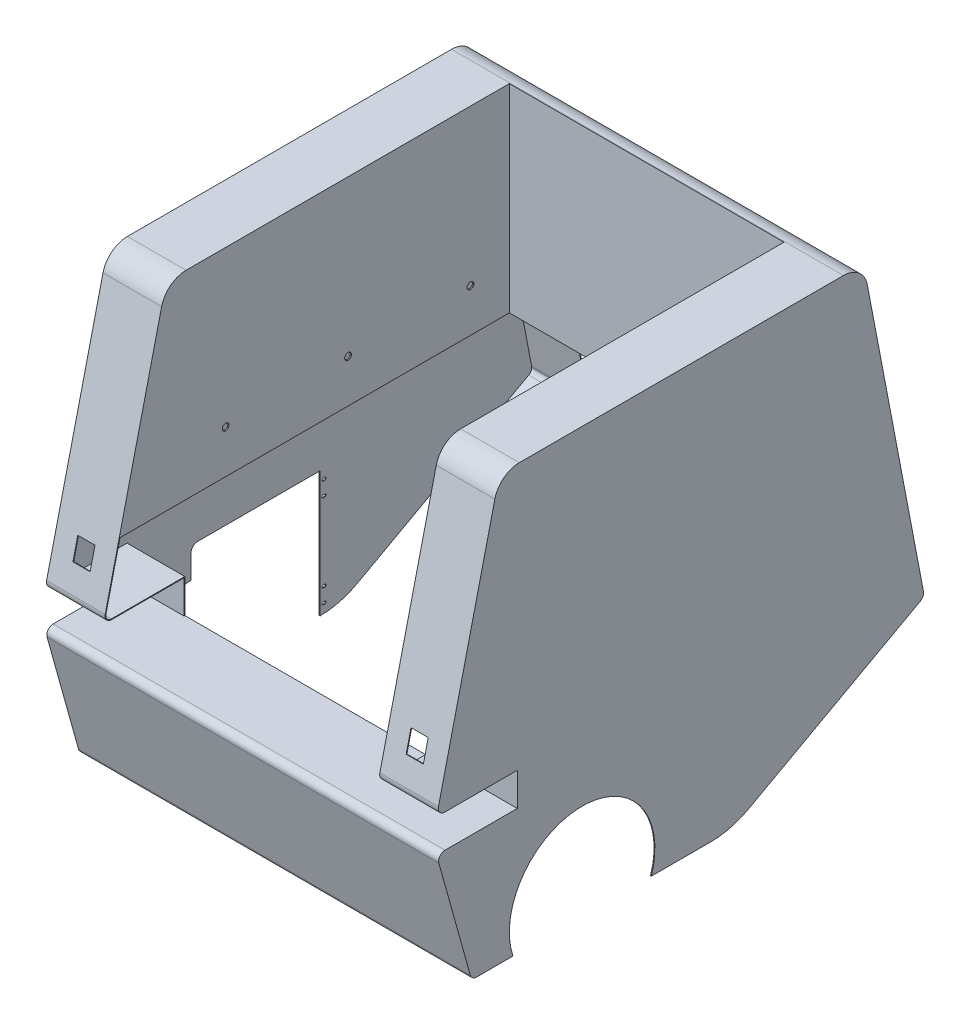
SolidWorks part; units mm, degrees
material "6061 합금"
ref_plane "정면" through (0, 0, 0) normal (0, 0, 1) x (1, 0, 0)
ref_plane "윗면" through (0, 0, 0) normal (0, 1, 0) x (1, 0, 0)
ref_plane "우측면" through (0, 0, 0) normal (1, 0, 0) x (0, 0, -1)
sketch "스케치1" plane through (0, 0, 0) normal (0, 1, 0) x (1, 0, 0)
  line L2 (-295, 336) -> (-295, -336)
  line L3 (-295, -336) -> (295, -336)
  line L4 (295, 336) -> (295, -336)
  line L5 (-295, 336) -> (295, -336) construction
  line L6 (-295, -336) -> (295, 336) construction
  line L8 (-295, 336) -> (-295, 399)
  line L9 (-295, 399) -> (295, 399)
  line L10 (295, 336) -> (295, 399)
  point P0 (0, 0)
  dimension "D1" = 590
  dimension "D2" = 672
  dimension "D3" = 63
extrude "보스-돌출1" add sketch "스케치1" along normal blind 640
shell "쉘1" thickness 1.2 removed face at (0, 0, -31.5) outward yes
sketch "스케치2" plane through (296.2, 0, 0) normal (1, 0, 0) x (0, 0, -1)
  line L0 (-212.2, 641.2) -> (-212.2, 0) construction
  line L1 (-337.2, 641.2) -> (400.2, 641.2) construction
  line L2 (-337.2, 0) -> (400.2, 0) construction
  line L3 (-337.2, 641.2) -> (-337.2, 0) construction
  line L4 (-182.2, 641.2) -> (-182.2, 0) construction
  line L5 (277.8, 641.2) -> (277.8, 160) construction
  line L6 (247.8, 641.2) -> (247.8, 160) construction
  line L8 (-212.2, 190) -> (277.8, 190) construction
  line L9 (-212.2, 160) -> (277.8, 160) construction
  line L10 (-212.2, 340) -> (277.8, 340) construction
  line L11 (-212.2, 310) -> (277.8, 310) construction
  line L12 (-212.2, 421) -> (277.8, 421) construction
  line L13 (-212.2, 391) -> (277.8, 391) construction
  line L14 (77.8, 0) -> (77.8, 190) construction
  line L15 (47.8, 190) -> (47.8, 0) construction
  line L16 (187.8, 190) -> (187.8, 160) construction
  line L17 (157.8, 190) -> (157.8, 160) construction
  line L18 (-147.2, 34) -> (-147.2, 0)
  line L19 (-147.2, 0) -> (-87.2, 0)
  line L20 (-87.2, 0) -> (-87.2, 34)
  line L21 (-215.2, 190) -> (-284.2, 190) construction
  line L22 (-284.2, 190) -> (-284.2, 195) construction
  line L23 (-284.2, 195) -> (-212.2, 195) construction
  line L24 (-215.2, 240) -> (-215.2, 190)
  line L25 (-284.2, 195) -> (-284.2, 240) construction
  line L26 (-284.2, 240) -> (-215.2, 240) construction
  line L29 (-333.7807, 177.7423) -> (-286.171, 7.0657)
  line L30 (-276.8646, 0) -> (77.8, 0)
  line L31 (-212.2, 641.2) -> (277.8, 641.2)
  line L32 (-324.4743, 190) -> (-215.2, 190)
  line L34 (-215.2, 240) -> (-324.9833, 240)
  line L35 (-248.2, 195) -> (-248.2, 240) construction
  line L36 (-334.3851, 251.8879) -> (-249.1125, 612.0072)
  line L40 (-212.2, 340) -> (-313.521, 340) construction
  line L42 (-337.2, 641.2) -> (400.2, 641.2) construction
  line L43 (313.8942, 611.3536) -> (398.832, 167.1542)
  line L44 (400.2, 641.2) -> (400.2, 0) construction
  line L45 (393.8102, 156.5036) -> (134.1176, 14.4009)
  line L46 (-337.2, 0) -> (400.2, 0) construction
  line L48 (-314.9744, 329.5224) -> (-326.4708, 280.9713) construction
  arc A0 (-87.2, 34) -> (-147.2, 34) centre (-117.2, 34) ccw
  arc A3 (-276.8646, 0) -> (-286.171, 7.0657) centre (-276.8646, 9.6617) cw
  arc A4 (-333.7807, 177.7423) -> (-324.4743, 190) centre (-324.4743, 180.3383) cw
  arc A5 (-324.9833, 240) -> (-334.3851, 251.8879) centre (-324.9833, 249.6617) cw
  arc A9 (398.832, 167.1542) -> (393.8102, 156.5036) centre (389.01, 165.2761) cw
  arc A11 (313.8942, 611.3536) -> (277.8, 641.2) centre (277.8, 604.4519) ccw
  arc A12 (77.8, 0) -> (134.1176, 14.4009) centre (77.8, 117.3212) ccw
  arc A13 (-212.2, 641.2) -> (-249.1125, 612.0072) centre (-212.2, 603.2667) ccw
  point P34 (187.8, 175)
  point P55 (-242.2, 641.2)
  point P63 (-284.2, 0)
  point P66 (-337.2, 190)
  point P69 (-337.2, 240)
  point P74 (307.8, 641.2)
  point P77 (107.8, 0)
  point P80 (400.2, 160)
  line M12 (-337.2, 0) -> (400.2, 0)
  line M14 (400.2, 641.2) -> (-337.2, 641.2)
  line M15 (-337.2, 641.2) -> (-337.2, 0)
  line M74 (400.2, 0) -> (400.2, 641.2)
  dimension "D17" = 60
  dimension "D23" = 30
  dimension "D24" = 30
  dimension "D27" = 10
  dimension "D30" = 1
  dimension "D1" = 125
  dimension "D2" = 30
  dimension "D3" = 490
  dimension "D4" = 30
  dimension "D5" = 190
  dimension "D6" = 30
  dimension "D7" = 150
  dimension "D8" = 30
  dimension "D9" = 81
  dimension "D10" = 30
  dimension "D11" = 290
  dimension "D12" = 30
  dimension "D13" = 110
  dimension "D14" = 30
  dimension "D15" = 95
  dimension "D16" = 34
  dimension "D18" = 72
  dimension "D19" = 5
  dimension "D20" = 45
  dimension "D22" = 30
  dimension "D28" = 3
  dimension "D29" = 72
extrude "컷-돌출1" cut sketch "스케치2" against normal up to next contours L34 A5 L36 A3 L29 A4 L32 M14 M15 M12 | L43 A9 L45 M12 M74 M14 region at (296.2, 6.5327, 307.0323) region at (296.2, 2.9619, -107.0426)
sketch "스케치3" plane through (-295, 0, 0) normal (1, 0, 0) x (0, 0, -1)
  line L10 (-247.9448, 611.7307) -> (-333.2174, 251.6114)
  line L11 (-324.9833, 241.2) -> (-214, 241.2)
  line L15 (-214, 241.2) -> (-214, 188.8)
  line L17 (-214, 188.8) -> (-324.4743, 188.8)
  line L18 (-332.6249, 178.0647) -> (-285.0151, 7.3881)
  line L20 (291.7052, 102) -> (393.2342, 157.5563)
  line L21 (397.8, 164.8576) -> (397.8, 165.6946)
  line L33 (397.6534, 166.9288) -> (312.7156, 611.1283)
  line L55 (287.1143, 640) -> (-221.6657, 640)
  line L56 (-249.1125, 612.0072) -> (-334.3851, 251.8879)
  line L58 (-324.9833, 240) -> (-215.2, 240)
  line L60 (-215.2, 240) -> (-215.2, 190)
  line L61 (-215.2, 190) -> (-324.4743, 190)
  line L62 (-333.7807, 177.7423) -> (-286.171, 7.0657)
  line L63 (-276.8646, 0) -> (77.8, 0)
  line L64 (134.1176, 14.4009) -> (393.8102, 156.5036)
  line L65 (399, 164.83) -> (399, 165.7222)
  line L66 (398.832, 167.1542) -> (313.8942, 611.3536)
  line L67 (287.1143, 640) -> (277.8, 640)
  line L68 (-249.1125, 612.0072) -> (-334.3851, 251.8879)
  line L69 (-324.9833, 240) -> (-215.2, 240)
  line L70 (-215.2, 240) -> (-215.2, 190)
  line L71 (-215.2, 190) -> (-324.4743, 190)
  line L72 (-333.7807, 177.7423) -> (-286.171, 7.0657)
  line L74 (292.2812, 100.9473) -> (393.8102, 156.5036)
  line L75 (399, 164.83) -> (399, 165.7222)
  line L76 (398.832, 167.1542) -> (313.8942, 611.3536)
  line L77 (277.8, 160) -> (277.8, 102) construction
  line L78 (277.8, 102) -> (298.7222, 102) construction
  line L79 (291.7052, 102) -> (292.2812, 100.9473)
  line L80 (134.1176, 14.4009) -> (393.8102, 156.5036) construction
  line L81 (133.5415, 15.4536) -> (393.2342, 157.5563) construction
  line L82 (-212.2, 640) -> (-221.6657, 640)
  line L83 (287.1143, 640) -> (-221.6657, 640) construction
  line L84 (-276.8646, 1.2) -> (-276.8646, 0)
  line L112 (286.9584, 638.8) -> (-221.5123, 638.8) construction
  line L113 (-276.8646, 1.2) -> (77.8, 1.2) construction
  line L114 (-276.8646, 0) -> (77.8, 0) construction
  arc A37 (-221.5123, 638.8) -> (-247.9448, 611.7307) centre (-212.2, 603.2667) ccw
  arc A38 (-333.2174, 251.6114) -> (-324.9833, 241.2) centre (-324.9833, 249.6617) ccw
  arc A39 (-324.4743, 188.8) -> (-332.6249, 178.0647) centre (-324.4743, 180.3383) ccw
  arc A40 (-285.0151, 7.3881) -> (-276.8646, 1.2) centre (-276.8646, 9.6617) ccw
  arc A42 (393.2342, 157.5563) -> (397.8, 164.8576) centre (389.01, 165.2761) ccw
  arc A43 (397.8, 165.6946) -> (397.6534, 166.9288) centre (389.01, 165.2761) ccw
  arc A45 (312.7156, 611.1283) -> (286.9584, 638.8) centre (277.8, 604.4519) ccw
  arc A55 (-221.6657, 640) -> (-249.1125, 612.0072) centre (-212.2, 603.2667) ccw
  arc A56 (-334.3851, 251.8879) -> (-324.9833, 240) centre (-324.9833, 249.6617) ccw
  arc A57 (-324.4743, 190) -> (-333.7807, 177.7423) centre (-324.4743, 180.3383) ccw
  arc A58 (-286.171, 7.0657) -> (-276.8646, 0) centre (-276.8646, 9.6617) ccw
  arc A59 (77.8, 0) -> (134.1176, 14.4009) centre (77.8, 117.3212) ccw
  arc A60 (393.8102, 156.5036) -> (399, 164.83) centre (389.01, 165.2761) ccw
  arc A61 (399, 165.7222) -> (398.832, 167.1542) centre (389.01, 165.2761) ccw
  arc A62 (313.8942, 611.3536) -> (287.1143, 640) centre (277.8, 604.4519) ccw
  arc A63 (-221.6657, 640) -> (-249.1125, 612.0072) centre (-212.2, 603.2667) ccw
  arc A64 (-334.3851, 251.8879) -> (-324.9833, 240) centre (-324.9833, 249.6617) ccw
  arc A65 (-324.4743, 190) -> (-333.7807, 177.7423) centre (-324.4743, 180.3383) ccw
  arc A66 (-286.171, 7.0657) -> (-276.8646, 0) centre (-276.8646, 9.6617) ccw
  arc A68 (393.8102, 156.5036) -> (399, 164.83) centre (389.01, 165.2761) ccw
  arc A72 (399, 165.7222) -> (398.832, 167.1542) centre (389.01, 165.2761) ccw
  arc A74 (313.8942, 611.3536) -> (287.1143, 640) centre (277.8, 604.4519) ccw
  arc A76 (286.9584, 638.8) -> (277.8, 640) centre (277.8, 604.4519) ccw
  arc A79 (-221.5123, 638.8) -> (-212.2, 640) centre (-212.2, 603.2667) cw
  arc A97 (77.8, 0) -> (134.1176, 14.4009) centre (77.8, 117.3212) ccw construction
  arc A98 (77.8, 1.2) -> (133.5415, 15.4536) centre (77.8, 117.3212) ccw construction
  line M28 (-249.1125, 612.0072) -> (-334.3851, 251.8879)
  arc M30 (-334.3851, 251.8879) -> (-324.9833, 240) centre (-324.9833, 249.6617) ccw
  line M31 (-324.9833, 240) -> (-215.2, 240)
  line M33 (-215.2, 190) -> (-324.4743, 190)
  arc M34 (-324.4743, 190) -> (-333.7807, 177.7423) centre (-324.4743, 180.3383) ccw
  line M35 (-333.7807, 177.7423) -> (-286.171, 7.0657)
  arc M36 (-286.171, 7.0657) -> (-276.8646, 0) centre (-276.8646, 9.6617) ccw
  line M43 (287.1143, 640) -> (-221.6657, 640)
  line M77 (134.1176, 14.4009) -> (393.8102, 156.5036)
  arc M78 (393.8102, 156.5036) -> (399, 164.83) centre (389.01, 165.2761) ccw
  line M79 (399, 164.83) -> (399, 165.7222)
  line M80 (398.832, 167.1542) -> (313.8942, 611.3536)
  line M121 (-215.2, 240) -> (-215.2, 190)
  arc M131 (399, 165.7222) -> (398.832, 167.1542) centre (389.01, 165.2761) ccw
  arc M132 (313.8942, 611.3536) -> (287.1143, 640) centre (277.8, 604.4519) ccw
  dimension "D2" = 1.2
  dimension "D3" = 58
  dimension "D1" = 0
extrude "보스-돌출2" add sketch "스케치3" along normal blind 590 contours A45 L33 M43 M28 M30 M31 M121 M33 M34 M35 M36 | M77 M78 M79 M131 M80 M132 M43 region at (-295, 431.8212, 291.2152) region at (-295, 629.1702, -304.241)
sketch "스케치4" plane through (-296.2, 0, 0) normal (-1, 0, 0) x (0, 0, 1)
  line L0 (-77.8, 190) -> (-77.8, 0)
  line L2 (-77.8, 0) -> (12.5864, 0)
  line L3 (147.2, 0) -> (147.2, 34)
  line L4 (87.2, 0) -> (147.2, 0)
  line L5 (87.2, 34) -> (87.2, 0)
  line L6 (147.2, 0) -> (147.2, 34)
  line L7 (87.2, 0) -> (147.2, 0)
  line L8 (87.2, 34) -> (87.2, 0)
  line L17 (286.171, 7.0657) -> (333.7807, 177.7423)
  line L18 (-77.8, 0) -> (276.8646, 0)
  line L21 (-393.8102, 156.5036) -> (-134.1176, 14.4009)
  line L22 (212.2, 641.2) -> (-277.8, 641.2)
  line L24 (334.3851, 251.8879) -> (249.1125, 612.0072)
  line L25 (215.2, 240) -> (324.9833, 240)
  line L26 (215.2, 190) -> (215.2, 240)
  line L27 (324.4743, 190) -> (215.2, 190)
  line L28 (286.171, 7.0657) -> (333.7807, 177.7423)
  line L29 (-77.8, 0) -> (276.8646, 0)
  line L33 (212.2, 641.2) -> (-277.8, 641.2)
  line L35 (334.3851, 251.8879) -> (249.1125, 612.0072)
  line L36 (215.2, 240) -> (324.9833, 240)
  line L38 (324.4743, 190) -> (215.2, 190)
  line L46 (215.2, 190) -> (215.2, 240)
  line L47 (215.2, 190) -> (215.2, 240)
  line L48 (215.2, 190) -> (215.2, 240)
  line L79 (117.2, 144) -> (117.2, 180)
  line L80 (212.2, 190) -> (-277.8, 190) construction
  line L81 (107.2, 190) -> (-77.8, 190)
  line L91 (-393.8102, 156.5036) -> (-134.1176, 14.4009)
  line L92 (-313.8942, 611.3536) -> (-398.832, 167.1542)
  line L93 (-313.8942, 611.3536) -> (-398.832, 167.1542)
  line L102 (286.171, 7.0657) -> (333.7807, 177.7423)
  line L103 (-77.8, 0) -> (276.8646, 0)
  line L105 (-393.8102, 156.5036) -> (-134.1176, 14.4009)
  line L106 (-313.8942, 611.3536) -> (-398.832, 167.1542)
  line L108 (212.2, 641.2) -> (-277.8, 641.2)
  line L110 (334.3851, 251.8879) -> (249.1125, 612.0072)
  line L111 (215.2, 240) -> (324.9833, 240)
  line L113 (324.4743, 190) -> (215.2, 190)
  line L114 (286.171, 7.0657) -> (333.7807, 177.7423)
  line L115 (-77.8, 0) -> (276.8646, 0)
  line L117 (-393.8102, 156.5036) -> (-134.1176, 14.4009)
  line L118 (-313.8942, 611.3536) -> (-398.832, 167.1542)
  line L120 (212.2, 641.2) -> (-277.8, 641.2)
  line L122 (334.3851, 251.8879) -> (249.1125, 612.0072)
  line L123 (215.2, 240) -> (324.9833, 240)
  line L125 (324.4743, 190) -> (215.2, 190)
  arc A0 (117.2, 180) -> (107.2, 190) centre (107.2, 180) ccw
  arc A1 (147.2, 34) -> (87.2, 34) centre (117.2, 34) ccw
  arc A2 (147.2, 34) -> (87.2, 34) centre (117.2, 34) ccw
  circle A3 centre (117.2, 34) radius 105 construction
  arc A8 (276.8646, 0) -> (286.171, 7.0657) centre (276.8646, 9.6617) ccw
  arc A9 (-134.1176, 14.4009) -> (-77.8, 0) centre (-77.8, 117.3212) ccw
  arc A11 (249.1125, 612.0072) -> (212.2, 641.2) centre (212.2, 603.2667) ccw
  arc A12 (324.9833, 240) -> (334.3851, 251.8879) centre (324.9833, 249.6617) ccw
  arc A13 (333.7807, 177.7423) -> (324.4743, 190) centre (324.4743, 180.3383) ccw
  arc A14 (276.8646, 0) -> (286.171, 7.0657) centre (276.8646, 9.6617) ccw
  arc A18 (324.9833, 240) -> (334.3851, 251.8879) centre (324.9833, 249.6617) ccw
  arc A19 (333.7807, 177.7423) -> (324.4743, 190) centre (324.4743, 180.3383) ccw
  arc A22 (-134.1176, 14.4009) -> (-77.8, 0) centre (-77.8, 117.3212) ccw
  arc A23 (-277.8, 641.2) -> (-313.8942, 611.3536) centre (-277.8, 604.4519) ccw
  arc A24 (-277.8, 641.2) -> (-313.8942, 611.3536) centre (-277.8, 604.4519) ccw
  arc A25 (-134.1176, 14.4009) -> (-77.8, 0) centre (-77.8, 117.3212) ccw
  arc A26 (-134.1176, 14.4009) -> (-77.8, 0) centre (-77.8, 117.3212) ccw
  arc A27 (-277.8, 641.2) -> (-313.8942, 611.3536) centre (-277.8, 604.4519) ccw
  arc A28 (-277.8, 641.2) -> (-313.8942, 611.3536) centre (-277.8, 604.4519) ccw
  arc A30 (249.1125, 612.0072) -> (212.2, 641.2) centre (212.2, 603.2667) ccw
  arc A31 (249.1125, 612.0072) -> (212.2, 641.2) centre (212.2, 603.2667) ccw
  arc A32 (249.1125, 612.0072) -> (212.2, 641.2) centre (212.2, 603.2667) ccw
  circle A38 centre (117.2, 34) radius 110
  arc A45 (-398.832, 167.1542) -> (-393.8102, 156.5036) centre (-389.01, 165.2761) ccw
  arc A46 (-398.832, 167.1542) -> (-393.8102, 156.5036) centre (-389.01, 165.2761) ccw
  arc A52 (276.8646, 0) -> (286.171, 7.0657) centre (276.8646, 9.6617) ccw
  arc A54 (-398.832, 167.1542) -> (-393.8102, 156.5036) centre (-389.01, 165.2761) ccw
  arc A57 (324.9833, 240) -> (334.3851, 251.8879) centre (324.9833, 249.6617) ccw
  arc A58 (333.7807, 177.7423) -> (324.4743, 190) centre (324.4743, 180.3383) ccw
  arc A59 (276.8646, 0) -> (286.171, 7.0657) centre (276.8646, 9.6617) ccw
  arc A61 (-398.832, 167.1542) -> (-393.8102, 156.5036) centre (-389.01, 165.2761) ccw
  arc A64 (324.9833, 240) -> (334.3851, 251.8879) centre (324.9833, 249.6617) ccw
  arc A65 (333.7807, 177.7423) -> (324.4743, 190) centre (324.4743, 180.3383) ccw
  point P42 (117.2, 190)
  line M24 (-77.8, 0) -> (276.8646, 0)
  dimension "D3" = 220
  dimension "D4" = 10
  dimension "D1" = 0
  dimension "D2" = 0
  dimension "D5" = 0
extrude "컷-돌출2" cut sketch "스케치4" against normal up to next contours A38 M24 | A38 L8 A2 L6 M24 | L6 A2 L8 M24 | A38 L79 A0 L81 L0 M24 region at (-296.2, 112.6357, -7.3305) region at (-296.2, 68.0406, 117.2) region at (-296.2, -31.53, 117.2) region at (-296.2, 29.1704, 117.2)
sketch "스케치5" plane through (296.2, 0, 0) normal (1, 0, 0) x (0, 0, -1)
  line L3 (-147.2, 34) -> (-147.2, 0)
  line L4 (-147.2, 0) -> (-87.2, 0)
  line L5 (-87.2, 0) -> (-87.2, 34)
  line L6 (-147.2, 34) -> (-147.2, 0)
  line L7 (-147.2, 0) -> (-87.2, 0)
  line L8 (-87.2, 0) -> (-87.2, 34)
  line L18 (-333.7807, 177.7423) -> (-286.171, 7.0657)
  line L19 (-276.8646, 0) -> (77.8, 0)
  line L21 (134.1176, 14.4009) -> (393.8102, 156.5036)
  line L22 (398.832, 167.1542) -> (313.8942, 611.3536)
  line L24 (277.8, 641.2) -> (-212.2, 641.2)
  line L26 (-249.1125, 612.0072) -> (-334.3851, 251.8879)
  line L27 (-324.9833, 240) -> (-215.2, 240)
  line L28 (-215.2, 240) -> (-215.2, 190)
  line L29 (-215.2, 190) -> (-324.4743, 190)
  line L30 (-333.7807, 177.7423) -> (-286.171, 7.0657)
  line L31 (-276.8646, 0) -> (77.8, 0)
  line L33 (134.1176, 14.4009) -> (393.8102, 156.5036)
  line L34 (398.832, 167.1542) -> (313.8942, 611.3536)
  line L36 (277.8, 641.2) -> (-212.2, 641.2)
  line L38 (-249.1125, 612.0072) -> (-334.3851, 251.8879)
  line L39 (-324.9833, 240) -> (-215.2, 240)
  line L41 (-215.2, 190) -> (-324.4743, 190)
  line L42 (-215.2, 240) -> (-215.2, 190)
  circle A0 centre (-117.2, 34) radius 110
  arc A1 (-87.2, 34) -> (-147.2, 34) centre (-117.2, 34) ccw
  arc A2 (-87.2, 34) -> (-147.2, 34) centre (-117.2, 34) ccw
  circle A3 centre (-117.2, 34) radius 105 construction
  arc A9 (-286.171, 7.0657) -> (-276.8646, 0) centre (-276.8646, 9.6617) ccw
  arc A10 (77.8, 0) -> (134.1176, 14.4009) centre (77.8, 117.3212) ccw
  arc A11 (393.8102, 156.5036) -> (398.832, 167.1542) centre (389.01, 165.2761) ccw
  arc A12 (77.8, 0) -> (134.1176, 14.4009) centre (77.8, 117.3212) ccw
  arc A13 (-212.2, 641.2) -> (-249.1125, 612.0072) centre (-212.2, 603.2667) ccw
  arc A14 (-334.3851, 251.8879) -> (-324.9833, 240) centre (-324.9833, 249.6617) ccw
  arc A15 (-324.4743, 190) -> (-333.7807, 177.7423) centre (-324.4743, 180.3383) ccw
  arc A16 (-286.171, 7.0657) -> (-276.8646, 0) centre (-276.8646, 9.6617) ccw
  arc A18 (393.8102, 156.5036) -> (398.832, 167.1542) centre (389.01, 165.2761) ccw
  arc A21 (-334.3851, 251.8879) -> (-324.9833, 240) centre (-324.9833, 249.6617) ccw
  arc A22 (-324.4743, 190) -> (-333.7807, 177.7423) centre (-324.4743, 180.3383) ccw
  arc A24 (313.8942, 611.3536) -> (277.8, 641.2) centre (277.8, 604.4519) ccw
  arc A25 (313.8942, 611.3536) -> (277.8, 641.2) centre (277.8, 604.4519) ccw
  arc A27 (-212.2, 641.2) -> (-249.1125, 612.0072) centre (-212.2, 603.2667) ccw
  line M26 (-276.8646, 0) -> (77.8, 0)
  dimension "D3" = 220
  dimension "D1" = 0
  dimension "D2" = 0
extrude "컷-돌출3" cut sketch "스케치5" against normal up to next contours A2 L8 A0 L31 L6 M26 | L8 A2 L6 M26 | L31 A0 M26 region at (296.2, 29.1704, 117.2) region at (296.2, 68.0406, 117.2) region at (296.2, -31.53, 117.2)
ref_plane "평면1" through (0, 0, 350) normal (0, 0, 1) x (1, 0, 0)
sketch "스케치6" plane through (0, 0, 350) normal (0, 0, 1) x (1, 0, 0)
  line L0 (0, 0) -> (0, 641.2) construction
  line L2 (-240, 421) -> (-240, 0) construction
  line L3 (-207.6, 641.2) -> (207.6, 641.2)
  line L4 (240, 421) -> (240, 0) construction
  line L5 (-210, 421) -> (-210, 0) construction
  line L6 (210, 0) -> (210, 421) construction
  line L7 (-240, 30) -> (240, 30) construction
  line L8 (-240, 0) -> (240, 0) construction
  line L9 (-240, 160) -> (240, 160) construction
  line L10 (-240, 190) -> (240, 190) construction
  line L11 (-240, 310) -> (240, 310) construction
  line L12 (-240, 340) -> (240, 340) construction
  line L13 (210, 421) -> (240, 421) construction
  line L14 (210, 391) -> (240, 391) construction
  line L15 (-240, 421) -> (-210, 421) construction
  line L16 (-240, 391) -> (-210, 391) construction
  line L17 (-207.6, 339) -> (207.6, 339)
  line L22 (-207.6, 339) -> (-207.6, 641.2)
  line L24 (207.6, 339) -> (207.6, 641.2)
  line L27 (-296.2, 641.2) -> (296.2, 641.2) construction
  point P29 (225, 421)
  dimension "D1" = 240
  dimension "D2" = 240
  dimension "D3" = 30
  dimension "D4" = 30
  dimension "D5" = 30
  dimension "D6" = 160
  dimension "D7" = 30
  dimension "D8" = 150
  dimension "D9" = 30
  dimension "D10" = 81
  dimension "D11" = 30
  dimension "D12" = 1
  dimension "D13" = 2.4
  dimension "D14" = 2.4
extrude "컷-돌출4" cut sketch "스케치6" against normal up to vertex contours L17 L24 L3 L22 region at (0, 490.1, 350) up to point (296.2, 641.2, -277.8)
ref_plane "평면2" through (0, 0, 313.7578) normal (0, 0, -1) x (-1, 0, 0)
sketch "스케치7" plane through (0, 0, 313.7578) normal (0, 0, -1) x (-1, 0, 0)
  line L17 (207.6, 339) -> (-207.6, 339) construction
  line L18 (207.6, 339) -> (-207.6, 339)
  line L19 (207.6, 339) -> (207.6, 341.4)
  line L20 (207.6, 339) -> (207.6, 641.2) construction
  line L21 (207.6, 341.4) -> (-207.6, 341.4)
  line L22 (-207.6, 339) -> (-207.6, 641.2) construction
  line L23 (-207.6, 341.4) -> (-207.6, 339)
  dimension "D1" = 2.4
extrude "보스-돌출3" add sketch "스케치7" along normal up to vertex contours L21 region at (0, 340.2, 313.7578) up to point (296.2, 421, -277.8)
sketch "스케치8" plane through (0, 0, 0) normal (1, 0, 0) x (0, 0, -1)
  line L8 (-313.7578, 341.4) -> (-313.7578, 339)
  line L9 (-313.7578, 339) -> (-313.1895, 341.4)
  line L10 (-313.1895, 341.4) -> (-313.7578, 341.4)
  line L11 (-313.7578, 341.4) -> (-313.7578, 339)
  line L12 (-313.7578, 339) -> (-313.1895, 341.4)
  line L13 (-313.1895, 341.4) -> (-313.7578, 341.4)
  dimension "D1" = 0
extrude "컷-돌출5" cut sketch "스케치8" against normal through all both and the other way through all
sketch "스케치10" plane through (0, 341.4, 0) normal (0, 1, 0) x (1, 0, 0)
  line L14 (-207.6, 276.6) -> (207.6, 276.6)
  line L16 (-207.6, 277.8) -> (-208.8, 277.8)
  line L18 (-296.2, 277.8) -> (-207.6, 277.8) construction
  line L19 (-208.8, 277.8) -> (-208.8, -212.2)
  line L20 (-296.2, -212.2) -> (-207.6, -212.2) construction
  line L22 (-208.8, -212.2) -> (-207.6, -212.2)
  line L23 (-207.6, -311.9563) -> (-207.6, -313.1895)
  line L24 (-207.6, -313.1895) -> (207.6, -313.1895)
  line L26 (207.6, -313.1895) -> (207.6, -311.9563)
  line L27 (207.6, -311.9563) -> (207.6, 277.8)
  line L28 (207.6, 277.8) -> (-207.6, 277.8)
  line L29 (-207.6, 277.8) -> (-207.6, -311.9563)
  line L30 (-207.6, -311.9563) -> (-207.6, -313.1895)
  line L32 (207.6, -313.1895) -> (207.6, -311.9563)
  line L33 (207.6, -311.9563) -> (207.6, 277.8)
  line L34 (207.6, 277.8) -> (-207.6, 277.8)
  line L35 (-207.6, 277.8) -> (-207.6, -311.9563)
  line L36 (207.6, -212.2) -> (208.8, -212.2)
  line L37 (207.6, -212.2) -> (296.2, -212.2) construction
  line L38 (208.8, -212.2) -> (208.8, 277.8)
  line L39 (207.6, 277.8) -> (296.2, 277.8) construction
  line L40 (208.8, 277.8) -> (207.6, 277.8)
  line M13 (207.6, 277.8) -> (-207.6, 277.8)
  line M22 (207.6, -311.9563) -> (207.6, 277.8)
  line M23 (-207.6, 277.8) -> (-207.6, -311.9563)
  dimension "D1" = 0
  dimension "D2" = 1.2
  dimension "D3" = 1.2
  dimension "D4" = 1.2
extrude "보스-돌출4" add sketch "스케치10" along normal up to vertex contours M13 region at (0, 341.4, -277.2) up to point (296.2, 641.2, -277.8)
extrude "보스-돌출7" add sketch "스케치10<3>" along normal up to vertex and the other way up to vertex contours M23 | L38 L40 L33 L36 M22 region at (-208.2, 341.4, -32.8) region at (208.2, 341.4, -32.8) up to point (296.2, 641.2, -277.8) other way up to point (207.6, 339, -277.8)
sketch "스케치10<3>" plane through (0, 341.4, 0) normal (0, 1, 0) x (1, 0, 0) same geometry as "스케치10"
sketch "스케치30" plane through (-207.6, 0, 0) normal (1, 0, 0) x (0, 0, -1)
  line L0 (-247.9448, 611.7307) -> (-333.2174, 251.6114) construction
  line L1 (-247.9448, 611.7307) -> (-312.5246, 339)
  line L2 (-212.2, 339) -> (-312.5246, 339)
  line L3 (-212.2, 641.2) -> (-212.2, 0) construction
  line L4 (277.8, 339) -> (-212.2, 339) construction
  line L5 (-212.2, 339) -> (-212.2, 640)
  arc A0 (-212.2, 640) -> (-247.9448, 611.7307) centre (-212.2, 603.2667) ccw construction
  arc A1 (-212.2, 640) -> (-247.9448, 611.7307) centre (-212.2, 603.2667) ccw
extrude "보스-돌출8" add sketch "스케치30" against normal blind 1.2
mirror "대칭 복사2" about plane through (0, 0, 0) normal (1, 0, 0) of "보스-돌출8"
ref_plane "평면3" through (0, 0, -410) normal (0, 0, 1) x (1, 0, 0)
sketch "스케치15" plane through (0, 0, -410) normal (0, 0, 1) x (1, 0, 0)
  line L1 (-210, 340) -> (210, 340)
  line L2 (-210, 421) -> (-210, 0) construction
  line L3 (210, 340) -> (-210, 340)
  line L4 (210, 340) -> (210, 100.9473)
  line L5 (210, 100.9473) -> (-210, 100.9473)
  line L6 (-210, 340) -> (-210, 100.9473)
  line L8 (295, 100.9473) -> (-295, 100.9473) construction
  line L9 (-240, 340) -> (240, 340) construction
  line L10 (210, 0) -> (210, 421) construction
extrude "컷-돌출6" cut sketch "스케치15" along normal up to vertex contours L1 L6 L5 L4 region at (0, 220.4736, -410) up to point (296.2, 340, -277.8)
sketch "스케치17" plane through (0, 341.4, 0) normal (0, 1, 0) x (1, 0, 0)
  line L1 (209.8, -212.2) -> (-209.8, -212.2) construction
  line L3 (-209.8, 277.8) -> (209.8, 277.8) construction
  line L4 (-209.8, 247.8) -> (209.8, 247.8) construction
  line L7 (-209.8, -182.2) -> (209.8, -182.2) construction
  line L8 (-139.8, 247.8) -> (-139.8, -182.2) construction
  line L9 (-109.8, 247.8) -> (-109.8, -182.2) construction
  line L10 (139.8, 247.8) -> (139.8, -182.2) construction
  line L11 (109.8, 247.8) -> (109.8, -182.2) construction
  line L12 (-209.8, 187.8) -> (209.8, 187.8) construction
  line L13 (-209.8, 157.8) -> (209.8, 157.8) construction
  line L14 (-209.8, 77.8) -> (209.8, 77.8) construction
  line L15 (-209.8, 47.8) -> (209.8, 47.8) construction
  line L18 (-296.2, 277.8) -> (296.2, 277.8) construction
  line L19 (208.8, -312.5246) -> (208.8, 277.8) construction
  line L20 (-208.8, 277.8) -> (-208.8, -312.5246) construction
  point P24 (0, 157.8)
  dimension "D1" = 30
  dimension "D2" = 30
  dimension "D3" = 70
  dimension "D4" = 30
  dimension "D5" = 70
  dimension "D6" = 30
  dimension "D7" = 60
  dimension "D8" = 30
  dimension "D9" = 80
  dimension "D10" = 30
  dimension "D11" = 1
  dimension "D12" = 1
sketch "스케치18" plane through (0, 341.4, 0) normal (0, 1, 0) x (1, 0, 0)
  line L5 (-240, -350) -> (240, -350) construction
  line L6 (206.6, 275.6) -> (-206.6, 275.6)
  line L7 (-206.6, 275.6) -> (-206.6, -349)
  line L8 (-206.6, -349) -> (206.6, -349)
  line L9 (207.6, 276.6) -> (-207.6, 276.6)
  line L10 (-207.6, 276.6) -> (-207.6, -313.1895)
  line L11 (-207.6, -313.1895) -> (207.6, -313.1895)
  line L12 (207.6, -313.1895) -> (207.6, 276.6)
  line L13 (207.6, 276.6) -> (-207.6, 276.6)
  line L14 (-207.6, 276.6) -> (-207.6, -350)
  line L15 (-207.6, -350) -> (207.6, -350)
  line L16 (207.6, -350) -> (207.6, 276.6)
  line L17 (206.6, -349) -> (206.6, 275.6)
  dimension "D1" = 0
  dimension "D2" = 1
extrude "컷-돌출7" cut sketch "스케치18" against normal up to vertex contours L14 L15 L16 L13 up to point (296.2, 190, 215.2)
sketch "스케치19" plane through (-296.2, 0, 0) normal (-1, 0, 0) x (0, 0, 1)
  line L0 (-77.8, 190) -> (-77.8, 0) construction
  line L1 (-77.8, 180) -> (-87.8, 180) construction
  line L2 (-77.8, 180) -> (-77.8, 150) construction
  line L3 (-77.8, 150) -> (-87.8, 150) construction
  line L4 (-87.8, 180) -> (-87.8, 150) construction
  line L5 (-82.8, 180) -> (-82.8, 156) construction
  line L6 (-87.8, 165) -> (-77.8, 165) construction
  line L7 (-84.8, 178) -> (-82.8, 178)
  line L8 (-82.8, 174) -> (-84.8, 174)
  line L9 (-82.8, 156) -> (-84.8, 156)
  line L10 (-84.8, 152) -> (-82.8, 152)
  line L11 (-104.315, 95) -> (-47.685, 95) construction
  line L12 (-87.8, 25) -> (-77.8, 25) construction
  line L13 (-82.8, 10) -> (-82.8, 40) construction
  line L14 (-87.8, 10) -> (-87.8, 40) construction
  line L15 (-77.8, 40) -> (-87.8, 40) construction
  line L16 (-77.8, 10) -> (-77.8, 40) construction
  line L17 (-77.8, 10) -> (-87.8, 10) construction
  line L22 (-84.8, 38) -> (-82.8, 38)
  line L23 (-82.8, 34) -> (-84.8, 34)
  line L24 (-82.8, 16) -> (-84.8, 16)
  line L25 (-84.8, 12) -> (-82.8, 12)
  line L26 (-82.8, 152) -> (-82.8, 150) construction
  arc A0 (-82.8, 174) -> (-82.8, 178) centre (-82.8, 176) ccw
  arc A2 (-84.8, 178) -> (-84.8, 174) centre (-84.8, 176) ccw
  arc A3 (-84.8, 152) -> (-84.8, 156) centre (-84.8, 154) cw
  arc A4 (-82.8, 156) -> (-82.8, 152) centre (-82.8, 154) cw
  arc A9 (-82.8, 34) -> (-82.8, 38) centre (-82.8, 36) ccw
  arc A10 (-84.8, 38) -> (-84.8, 34) centre (-84.8, 36) ccw
  arc A11 (-84.8, 12) -> (-84.8, 16) centre (-84.8, 14) cw
  arc A12 (-82.8, 16) -> (-82.8, 12) centre (-82.8, 14) cw
  point P30 (-76, 95)
  dimension "D5" = 4
  dimension "D1" = 10
  dimension "D2" = 30
  dimension "D3" = 10
  dimension "D4" = 22
extrude "컷-돌출8" cut sketch "스케치19" against normal up to next
sketch "스케치20" plane through (0, 79.4689, -415.5988) normal (0, 0.1878, -0.9822) x (-1, 0, 0)
  line L9 (-210, 265.4807) -> (210, 265.4807) construction
  line L10 (-210, 265.4807) -> (210, 265.4807)
  line L11 (-210, 265.2513) -> (210, 265.2513) construction
  line L12 (-210, 265.2513) -> (210, 265.2513)
  line L13 (-210, 265.4807) -> (-210, 265.2513)
  line L14 (210, 265.4807) -> (210, 265.2513)
extrude "컷-돌출9" cut sketch "스케치20" against normal up to next
sketch "스케치21" plane through (0, 79.4689, -415.5988) normal (0, 0.1878, -0.9822) x (-1, 0, 0)
  line L0 (0, 0) -> (0, 576.451) construction
  line L2 (166, 270.4807) -> (166, 272.4807)
  line L8 (-190, 265.4807) -> (-160, 265.4807) construction
  line L13 (-190, 265.4807) -> (-190, 275.4807) construction
  line L14 (-190, 275.4807) -> (-160, 275.4807) construction
  line L23 (-160, 265.4807) -> (-160, 275.4807) construction
  line L24 (-190, 270.4807) -> (-160, 270.4807) construction
  line L25 (-175, 275.4807) -> (-175, 265.4807) construction
  line L26 (-184, 270.4807) -> (-184, 272.4807)
  line L27 (-188, 270.4807) -> (-188, 272.4807)
  line L28 (-162, 270.4807) -> (-162, 272.4807)
  line L29 (-166, 270.4807) -> (-166, 272.4807)
  line L30 (162, 270.4807) -> (162, 272.4807)
  line L31 (188, 270.4807) -> (188, 272.4807)
  line L32 (184, 270.4807) -> (184, 272.4807)
  line L34 (-210, 89.2739) -> (-210, 265.4807) construction
  line L36 (210, 265.4807) -> (-210, 265.4807) construction
  arc A8 (-188, 270.4807) -> (-184, 270.4807) centre (-186, 270.4807) ccw
  arc A10 (-184, 272.4807) -> (-188, 272.4807) centre (-186, 272.4807) ccw
  arc A11 (-166, 272.4807) -> (-162, 272.4807) centre (-164, 272.4807) cw
  arc A12 (-162, 270.4807) -> (-166, 270.4807) centre (-164, 270.4807) cw
  arc A13 (162, 270.4807) -> (166, 270.4807) centre (164, 270.4807) ccw
  arc A14 (166, 272.4807) -> (162, 272.4807) centre (164, 272.4807) ccw
  arc A15 (184, 272.4807) -> (188, 272.4807) centre (186, 272.4807) cw
  arc A16 (188, 270.4807) -> (184, 270.4807) centre (186, 270.4807) cw
  dimension "D5" = 4
  dimension "D1" = 20
  dimension "D2" = 30
  dimension "D3" = 10
  dimension "D4" = 22
extrude "컷-돌출10" cut sketch "스케치21" against normal up to next contours L26 A10 L27 A8 | A12 L28 A11 L29 | L2 A14 L30 A13 | A16 L31 A15 L32 region at (-164, 346.1186, -364.6112) region at (186, 346.1186, -364.6112) region at (164, 346.1186, -364.6112) region at (-186, 346.1186, -364.6112)
sketch "스케치22" plane through (0, 79.4689, -415.5988) normal (0, 0.1878, -0.9822) x (-1, 0, 0)
  line L1 (4.8497, 491.5212) -> (2.4249, 495.7212)
  line L2 (2.4249, 495.7212) -> (-2.4249, 495.7212)
  line L3 (-2.4249, 495.7212) -> (-4.8497, 491.5212)
  line L4 (-4.8497, 491.5212) -> (-2.4249, 487.3212)
  line L5 (-2.4249, 487.3212) -> (2.4249, 487.3212)
  line L6 (2.4249, 487.3212) -> (4.8497, 491.5212)
  line L7 (296.2, 541.5212) -> (-296.2, 541.5212) construction
  circle A0 centre (0, 491.5212) radius 4.2 construction
  point P10 (0, 0)
  dimension "D1" = 8.4
  dimension "D2" = 50
extrude "컷-돌출11" cut sketch "스케치22" against normal up to next
sketch "스케치31" plane through (207.6, 0, 0) normal (-1, 0, 0) x (0, 0, 1)
  line L0 (-277.8, 406) -> (212.2, 406) construction
  line L1 (-277.8, 641.2) -> (-277.8, 160) construction
  line L2 (212.2, 641.2) -> (212.2, 0) construction
  line L3 (212.2, 421) -> (-277.8, 421) construction
  line L4 (-247.8, 641.2) -> (-247.8, 160) construction
  line L5 (182.2, 641.2) -> (182.2, 0) construction
  point P8 (-32.8, 406)
  point P9 (152.2, 406)
  point P10 (-217.8, 406)
  dimension "D1" = 15
  dimension "D2" = 30
  dimension "D3" = 30
hole_wizard "M5 접시 머리 나사용 카운터싱크1" positions "스케치32" profile "스케치33" countersink size "M5" standard "ISO" end condition up to next
sketch "스케치32" plane through (207.6, 0, 0) normal (-1, 0, 0) x (0, 0, 1)
  point P0 (-217.8, 406)
  point P3 (-32.8, 406)
  point P6 (152.2, 406)
sketch "스케치33" plane through (207.6, 406, -217.8) normal (0, 1, 0) x (0, 0, 1)
  line L0 (0, 0) -> (0, 88.6)
  line L1 (0, 88.6) -> (2.75, 88.6)
  line L2 (2.75, 88.6) -> (2.75, 2.75)
  line L3 (2.75, 2.75) -> (5.2, 0.3)
  line L4 (5.2, 0.3) -> (5.2, 0)
  line L6 (5.2, 0) -> (0, 0)
  line L7 (-2.75, 2.75) -> (-5.2, 0.3) construction
  line L11 (0, -6.35) -> (0, 107.95) construction
  dimension "관통 구멍 지름" = 5.5
  dimension "관통 구멍 깊이" = 88.6
  dimension "카운터싱크 지름" = 10.4
  dimension "카운터싱크 각도" = 90
  dimension "머리 여유값" = 0.3
mirror "대칭 복사3" about plane through (0, 0, 0) normal (1, 0, 0) of "M5 접시 머리 나사용 카운터싱크1"
sketch "스케치27" plane through (0, 88.3485, 373.1095) normal (0, 0.2304, 0.9731) x (1, 0, 0)
  line L0 (251.9, 168.0617) -> (251.9, 305.8083) construction
  line L1 (207.6, 168.0617) -> (296.2, 168.0617) construction
  line L3 (196.2, 268.0617) -> (266.9107, 197.351) construction
  line L4 (238.9, 231.8617) -> (238.9, 236.8617)
  line L5 (241.9, 213.8617) -> (261.9, 213.8617) construction
  line L6 (241.9, 213.8617) -> (241.9, 210.8617) construction
  line L7 (207.6, 538.1392) -> (207.6, 168.0617)
  line L8 (207.6, 168.0617) -> (296.2, 168.0617)
  line L9 (296.2, 168.0617) -> (296.2, 538.1392)
  line L10 (207.6, 538.1392) -> (207.6, 168.0617)
  line L12 (207.6, 168.0617) -> (296.2, 168.0617) construction
  line L13 (296.2, 168.0617) -> (296.2, 538.1392) construction
  line L15 (241.9, 210.8617) -> (261.9, 210.8617) construction
  line L16 (261.9, 213.8617) -> (261.9, 210.8617) construction
  line L17 (241.9, 213.8617) -> (261.9, 210.8617) construction
  line L18 (241.9, 210.8617) -> (261.9, 213.8617) construction
  line L19 (241.9, 213.8617) -> (261.9, 213.8617) construction
  line L20 (241.9, 213.8617) -> (241.9, 225.8617) construction
  line L21 (241.9, 225.8617) -> (261.9, 225.8617) construction
  line L22 (261.9, 213.8617) -> (261.9, 225.8617) construction
  line L23 (238.9, 204.8617) -> (264.9, 204.8617)
  line L24 (238.9, 204.8617) -> (238.9, 231.8617)
  line L25 (238.9, 231.8617) -> (264.9, 231.8617) construction
  line L26 (264.9, 204.8617) -> (264.9, 231.8617)
  line L27 (238.9, 204.8617) -> (264.9, 231.8617) construction
  line L28 (238.9, 231.8617) -> (264.9, 204.8617) construction
  line L29 (238.9, 236.8617) -> (264.9, 236.8617)
  line L30 (264.9, 236.8617) -> (264.9, 231.8617)
  line L34 (296.2, 538.1392) -> (207.6, 538.1392)
  line L35 (296.2, 538.1392) -> (207.6, 538.1392)
  circle A0 centre (196.2, 268.0617) radius 100 construction
  point P4 (251.9, 212.3617)
  point P12 (251.9, 212.3617)
  point P19 (251.9, 218.3617)
  dimension "D3" = 200
  dimension "D1" = 0
  dimension "D2" = 44.3
  dimension "D4" = 45
  dimension "D5" = 20
  dimension "D6" = 3
  dimension "D7" = 12
  dimension "D8" = 7.5
  dimension "D9" = 6
  dimension "D10" = 3
  dimension "D11" = 5
extrude "컷-돌출14" cut sketch "스케치27" against normal up to next contours L30 L29 L4 L24 L23 L26 region at (251.9, 303.2672, 322.219)
mirror "대칭 복사4" about plane through (0, 0, 0) normal (1, 0, 0) of "컷-돌출14"
sketch "스케치35" plane through (-207.6, 0, 0) normal (1, 0, 0) x (0, 0, -1)
  line L0 (-247.9448, 611.7307) -> (-333.2174, 251.6114) construction
  line L1 (-312.0511, 341) -> (-312.5246, 339)
  line L2 (-312.0511, 341) -> (277.8, 341)
  line L3 (277.8, 641.2) -> (277.8, 160) construction
  line L4 (-312.5246, 339) -> (276.6, 339) construction
  line L5 (277.8, 341) -> (277.8, 339)
  line L7 (277.8, 339) -> (-312.5246, 339) construction
  line L8 (277.8, 339) -> (-312.5246, 339)
  dimension "D1" = 2
extrude "컷-돌출15" cut sketch "스케치35" against normal up to next and the other way up to next
